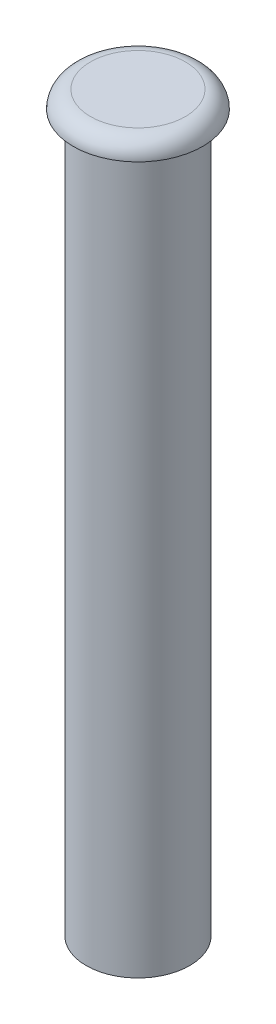
SolidWorks part; units mm, degrees
ref_plane "Front Plane" through (0, 0, 0) normal (0, 0, 1) x (1, 0, 0)
ref_plane "Top Plane" through (0, 0, 0) normal (0, 1, 0) x (1, 0, 0)
ref_plane "Right Plane" through (0, 0, 0) normal (1, 0, 0) x (0, 0, -1)
sketch "Sketch1" plane through (0, 0, 0) normal (0, 1, 0) x (1, 0, 0)
  circle A0 centre (0, 0) radius 6
  dimension "D1" = 12
extrude "Boss-Extrude1" add sketch "Sketch1" along normal blind 83
sketch "Sketch2" plane through (0, 83, 0) normal (0, 1, 0) x (1, 0, 0)
  circle A0 centre (0, 0) radius 7.5
  dimension "D1" = 15
extrude "Boss-Extrude2" add sketch "Sketch2" along normal blind 2
fillet "Fillet1" radius 2 1 edges at (0, 85, 7.5)
sketch "Sketch3" plane through (0, 0, 0) normal (0, -1, 0) x (1, 0, 0)
  circle A0 centre (0, 0) radius 2
  dimension "D1" = 4
extrude "Cut-Extrude1" cut sketch "Sketch3" against normal blind 5
